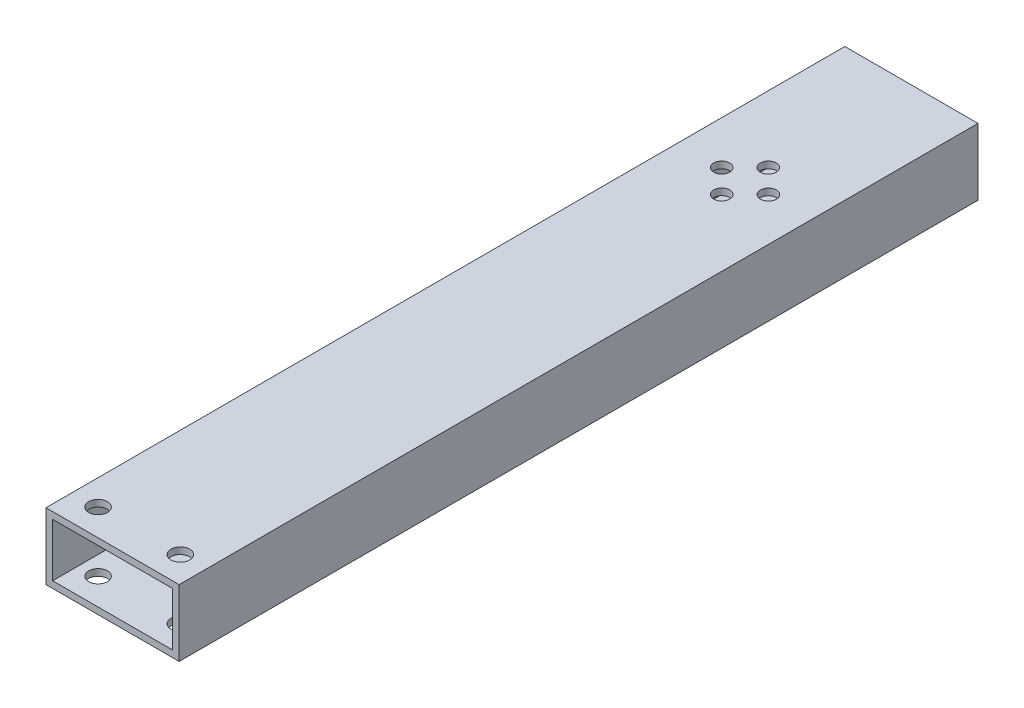
SolidWorks part; units mm, degrees
material "6061 Alloy"
ref_plane "Front Plane" through (0, 0, 0) normal (0, 0, 1) x (1, 0, 0)
ref_plane "Top Plane" through (0, 0, 0) normal (0, 1, 0) x (1, 0, 0)
ref_plane "Right Plane" through (0, 0, 0) normal (1, 0, 0) x (0, 0, -1)
sketch "Sketch1" plane through (0, 0, 0) normal (0, 0, 1) x (1, 0, 0)
  line L1 (-12.7, 6.35) -> (12.7, 6.35)
  line L2 (-12.7, 6.35) -> (-12.7, -6.35)
  line L3 (-12.7, -6.35) -> (12.7, -6.35)
  line L4 (12.7, 6.35) -> (12.7, -6.35)
  point P4 (-12.7, 0)
  point P6 (0, 6.35)
  dimension "D1" = 12.7
  dimension "D2" = 25.4
extrude "Boss-Extrude1" add sketch "Sketch1" along normal blind 127
sketch "Sketch4" plane through (0, 0, 0) normal (0, 0, -1) x (-1, 0, 0)
  line L0 (-12.7, -6.35) -> (-12.7, 6.35) construction
  line L1 (-11.43, 5.08) -> (11.43, 5.08)
  line L2 (-11.43, 5.08) -> (-11.43, -5.08)
  line L3 (-11.43, -5.08) -> (11.43, -5.08)
  line L4 (11.43, 5.08) -> (11.43, -5.08)
  line L5 (-12.7, 6.35) -> (12.7, 6.35) construction
  line L6 (12.7, -6.35) -> (-12.7, -6.35) construction
  line L7 (12.7, 6.35) -> (12.7, -6.35) construction
  dimension "D1" = 1.27
  dimension "D2" = 1.27
  dimension "D3" = 1.27
  dimension "D4" = 1.27
extrude "Cut-Extrude1" cut sketch "Sketch4" against normal through all
sketch "Sketch5" plane through (0, 6.35, 0) normal (0, 1, 0) x (1, 0, 0)
  line L0 (-12.7, -127) -> (-12.7, 0) construction
  line L1 (12.7, -127) -> (12.7, 0) construction
  line L2 (12.7, -127) -> (-12.7, -127) construction
  circle A0 centre (-7.8486, -121.92) radius 1.7907
  circle A1 centre (7.8486, -121.92) radius 1.7907
  dimension "D1" = 3.5814
  dimension "D2" = 3.5814
  dimension "D3" = 4.8514
  dimension "D4" = 4.8514
  dimension "D5" = 5.08
  dimension "D6" = 5.08
extrude "Cut-Extrude2" cut sketch "Sketch5" against normal through all both and the other way through all
sketch "Sketch6" plane through (0, -6.35, 0) normal (0, -1, 0) x (-1, 0, 0)
  line L0 (12.7, 0) -> (-12.7, 0) construction
  line L1 (12.7, -127) -> (12.7, 0) construction
  line L2 (12.7, -127) -> (-12.7, -127) construction
  circle A0 centre (4.445, -6.35) radius 1.524
  circle A1 centre (-4.4704, -6.35) radius 1.524
  circle A2 centre (0, -6.35) radius 4.445 construction
  circle A3 centre (0, -1.905) radius 1.524
  circle A4 centre (0, -10.795) radius 1.524
  dimension "D1" = 3.048
  dimension "D2" = 3.048
  dimension "D6" = 8.89
  dimension "D7" = 3.048
  dimension "D8" = 3.048
  dimension "D3" = 8.9154
  dimension "D4" = 6.35
  dimension "D5" = 8.255
  dimension "D9" = 116.205
  dimension "D10" = 120.65
extrude "Cut-Extrude3" cut sketch "Sketch6" against normal through all both contours A3 | A1 | A4 | A0
sketch "Sketch7" plane through (0, 0, 0) normal (0, 0, -1) x (-1, 0, 0)
  line L1 (-12.7, 6.35) -> (12.7, 6.35)
  line L2 (-12.7, 6.35) -> (-12.7, -6.35)
  line L3 (-12.7, -6.35) -> (12.7, -6.35)
  line L4 (12.7, 6.35) -> (12.7, -6.35)
  line L5 (-11.43, 5.08) -> (11.43, 5.08)
  line L6 (-11.43, 5.08) -> (-11.43, -5.08)
  line L7 (-11.43, -5.08) -> (11.43, -5.08)
  line L8 (11.43, 5.08) -> (11.43, -5.08)
extrude "Boss-Extrude2" add sketch "Sketch7" along normal blind 25.4
